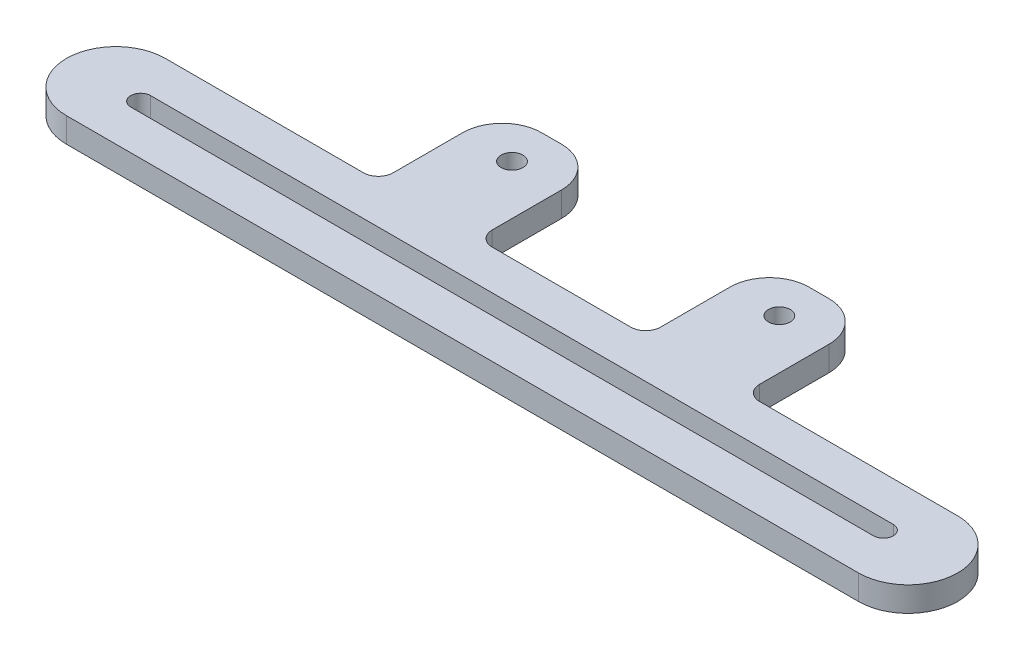
SolidWorks part; units mm, degrees
ref_plane "Front Plane" through (0, 0, 0) normal (0, 0, 1) x (1, 0, 0)
ref_plane "Top Plane" through (0, 0, 0) normal (0, 1, 0) x (1, 0, 0)
ref_plane "Right Plane" through (0, 0, 0) normal (1, 0, 0) x (0, 0, -1)
ref_axis "Axis_Z_Z_top" through (0, -55, 0) along (0, 1, 0)
ref_axis "Axis_X_Z_top" through (0, 0, -88.99) along (0, 0, 1)
ref_axis "Axis_Y_Z_top" through (-88.99, 0, 0) along (1, 0, 0)
sketch "Sketch1" plane through (0, 0, 0) normal (0, 1, 0) x (1, 0, 0)
  line L0 (0, 0) -> (160, 0) construction
  line L1 (0, 10) -> (43, 10)
  line L2 (0, -10) -> (160, -10)
  line L3 (5, 0) -> (155, 0) construction
  line L4 (5, 2) -> (155, 2)
  line L5 (5, -2) -> (155, -2)
  line L6 (80, 10) -> (80, 23.2321) construction
  line L8 (43, 10) -> (43, 27)
  line L9 (51, 35) -> (55, 35)
  line L10 (63, 10) -> (63, 27)
  line L12 (97, 10) -> (97, 27)
  line L13 (105, 35) -> (109, 35)
  line L14 (117, 10) -> (117, 27)
  line L15 (53, 35) -> (53, 27) construction
  line L16 (107, 35) -> (107, 27) construction
  line L17 (63, 10) -> (97, 10)
  line L18 (117, 10) -> (160, 10)
  arc A0 (0, 10) -> (0, -10) centre (0, 0) ccw
  arc A1 (160, -10) -> (160, 10) centre (160, 0) ccw
  arc A2 (5, 2) -> (5, -2) centre (5, 0) ccw
  arc A3 (155, -2) -> (155, 2) centre (155, 0) ccw
  circle A4 centre (53, 27) radius 2.2
  circle A5 centre (107, 27) radius 2.2
  arc A6 (109, 35) -> (117, 27) centre (109, 27) cw
  arc A7 (97, 27) -> (105, 35) centre (105, 27) cw
  arc A8 (55, 35) -> (63, 27) centre (55, 27) cw
  arc A9 (43, 27) -> (51, 35) centre (51, 27) cw
  point P3 (80, 0)
  point P10 (80, 0)
  point P33 (117, 35)
  point P36 (97, 35)
  point P39 (63, 35)
  point P42 (43, 35)
  dimension "D10" = 8
  dimension "D11" = 8
  dimension "D12" = 54
  dimension "D13" = 4.4
  dimension "D14" = 4.4
  dimension "D15" = 8
  dimension "D1" = 20
  dimension "D2" = 160
  dimension "D3" = 4
  dimension "D4" = 5
  dimension "D5" = 5
  dimension "D6" = 20
  dimension "D7" = 20
  dimension "D8" = 25
  dimension "D9" = 25
extrude "Boss-Extrude1" add sketch "Sketch1" along normal blind 5
fillet "Fillet1" radius 3 4 edges at (117, 2.5, -10) (97, 2.5, -10) (63, 2.5, -10) (43, 2.5, -10)
